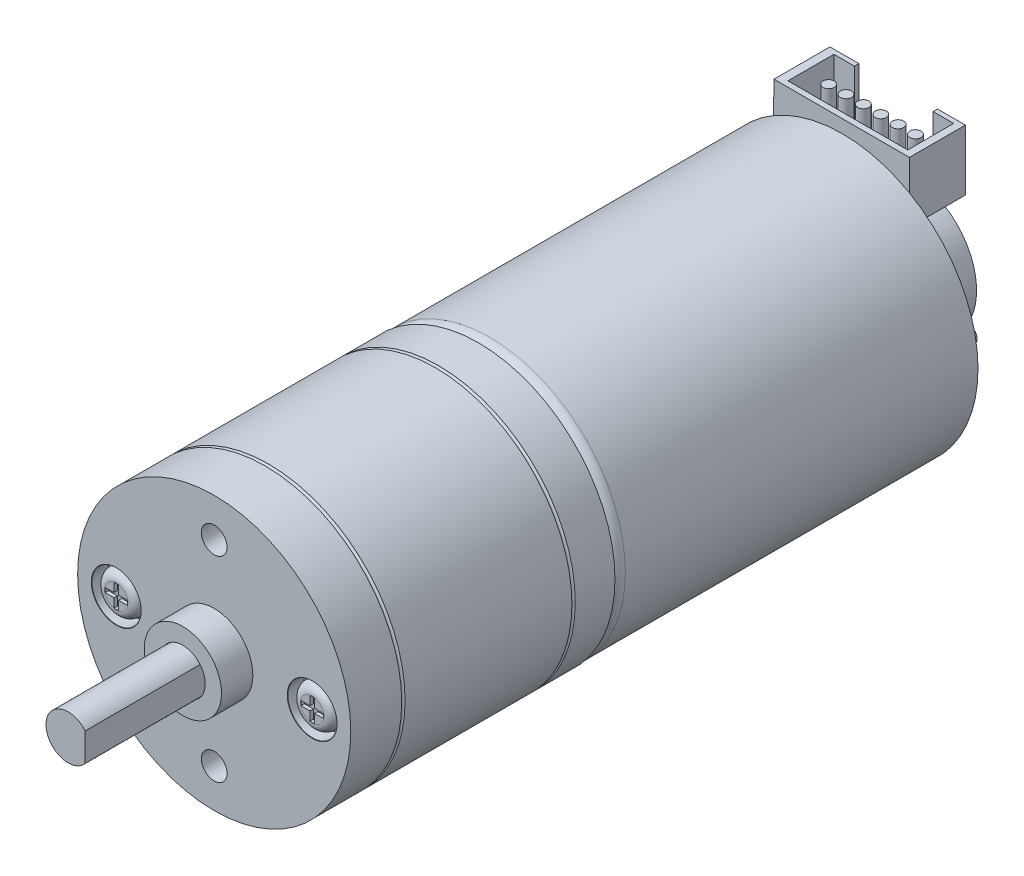
SolidWorks part; units mm, degrees
ref_plane "Front Plane" through (0, 0, 0) normal (0, 0, 1) x (1, 0, 0)
ref_plane "Top Plane" through (0, 0, 0) normal (0, 1, 0) x (1, 0, 0)
ref_plane "Right Plane" through (0, 0, 0) normal (1, 0, 0) x (0, 0, -1)
sketch "Sketch1" plane through (0, 0, 0) normal (0, 0, 1) x (1, 0, 0)
  circle A0 centre (0, 0) radius 12.125
  dimension "D1" = 24.25
extrude "Boss-Extrude1" add sketch "Sketch1" along normal blind 31
sketch "Sketch2" plane through (0, 0, 0) normal (0, 0, -1) x (-1, 0, 0)
  circle A1 centre (0, 0) radius 12.125
  circle A2 centre (0, 0) radius 12.125
  dimension "D1" = 0
fillet "Fillet2" radius 1 1 edges at (12.125, 0, 31)
shell "Shell1" thickness 1 removed face at (11.125, 0, 31)
ref_plane "Plane2" through (0, 0, 31) normal (0, 0, 1) x (1, 0, 0)
sketch "Sketch11" plane through (0, 0, 31) normal (0, 0, 1) x (1, 0, 0)
  circle A0 centre (0, 0) radius 12.2
  dimension "D1" = 24.4
extrude "Boss-Extrude4" add sketch "Sketch11" along normal blind 23.6 separate body
sketch "Sketch12" plane through (0, 0, 54.6) normal (0, 0, 1) x (1, 0, 0)
  circle A0 centre (0, 0) radius 3.45
  circle A1 centre (0, 0) radius 2
  dimension "D1" = 6.9
  dimension "D2" = 4
extrude "Boss-Extrude5" add sketch "Sketch12" along normal blind 2.8
sketch "Sketch14" plane through (0, 0, 54.6) normal (0, 0, 1) x (1, 0, 0)
  circle A0 centre (0, 0) radius 1.975
  dimension "D1" = 3.95
extrude "Boss-Extrude6" add sketch "Sketch14" along normal blind 13.05
sketch "Sketch16" plane through (0, 0, 67.65) normal (0, 0, 1) x (1, 0, 0)
  line L0 (-1.975, 0) -> (1.525, 0) construction
  line L1 (1.525, 0) -> (1.525, 1.255)
  line L2 (1.525, 0) -> (1.525, -1.255)
  circle A0 centre (0, 0) radius 1.975 construction
  arc A1 (1.525, -1.255) -> (1.525, 1.255) centre (0, 0) ccw
  dimension "D1" = 3.5
extrude "Cut-Extrude5" cut sketch "Sketch16" against normal up to surface (13.05 mm away) up to face at (3.45, 0, 54.6)
sketch "Sketch17" plane through (0, 0, 0) normal (0, 1, 0) x (1, 0, 0)
  line L0 (-12.2, -54.6) -> (-12.2, -49.9) construction
  line L1 (-12.2, -31) -> (-12.2, -54.6) construction
  line L2 (-12.2, -31) -> (-12.2, -34.7) construction
  circle A0 centre (-12.2, -49.9) radius 0.15
  circle A1 centre (-12.2, -34.7) radius 0.15
  dimension "D2" = 0.3
  dimension "D1" = 4.7
ref_axis "Axis1" through (0, 0, 54.6) along (0, 0, -1)
revolve "Cut-Revolve1" cut sketch "Sketch17" angle 360 about axis through (0, 0, 54.6) along (0, 0, -1)
sketch "Sketch18" plane through (0, 0, 54.6) normal (0, 0, 1) x (1, 0, 0)
  line L0 (0, 0) -> (8.75, 0) construction
  line L1 (0, 0) -> (0, 8.75) construction
  circle A1 centre (0, 8.75) radius 1.15
  circle A3 centre (0, -8.75) radius 1.15
  dimension "D3" = 2.3
extrude "Cut-Extrude7" cut sketch "Sketch18" against normal blind 10
sketch "Sketch19" plane through (0, 0, 0) normal (1, 0, 0) x (0, 0, -1)
  line L0 (-54.6, 9.9) -> (-53.4944, 10.0329)
  line L1 (-54.6, 9.9) -> (-54.6, 7.6) construction
  line L2 (-54.6, 12.2) -> (-54.6, -12.2) construction
  line L3 (-53.4944, 10.0329) -> (-53.399, 9.9)
  line L4 (-53.399, 9.9) -> (-54.6, 9.9)
sketch "Sketch20" plane through (0, 0, 54.6) normal (0, 0, 1) x (1, 0, 0)
  circle A0 centre (0, 8.75) radius 1.1448
curve "Helix/Spiral1" pitch 0.5 height 6 turns 12
sketch "Sketch21" plane through (0, 0, 54.6) normal (0, 0, 1) x (1, 0, 0)
  line L0 (0, 0) -> (0, -5.9622) construction
  circle A1 centre (8.75, 0) radius 2.25
  circle A2 centre (-8.75, 0) radius 2.25
  dimension "D1" = 4.5
hole_wizard "CBORE for M2 Cheese Head Screw1" positions "3DSketch1" profile "Sketch23" counterbore size "M2" standard "DIN"
sketch3d "3DSketch1"
  point P0 (-8.75, 0, 54.6)
  point P3 (8.75, 0, 54.6)
sketch "Sketch23" plane through (-8.75, 0, 54.6) normal (1, 0, 0) x (0, -1, 0)
  line L0 (0, 0) -> (0, 5.7811)
  line L1 (0, 5.7811) -> (1.3, 5)
  line L2 (1.3, 5) -> (1.3, 1.4)
  line L3 (1.3, 1.4) -> (2.2, 1.4)
  line L5 (2.2, 1.4) -> (2.2, 0.025)
  line L6 (2.2, 0.025) -> (2.225, 0)
  line L7 (2.225, 0) -> (0, 0)
  line L8 (-2.2, 0.025) -> (-2.225, 0) construction
  line L10 (0, 5.7811) -> (-1.3, 5) construction
  line L11 (0, -6.35) -> (0, 107.95) construction
  dimension "Hole Dia." = 2.6
  dimension "Hole Depth" = 5
  dimension "C'Bore Dia." = 4.4
  dimension "C'Bore Depth" = 1.4
  dimension "Near C'Sink Dia." = 4.45
  dimension "Near C'Sink Angle" = 90
  dimension "Drill Angle" = 118
sketch "Sketch24" plane through (0, 0, 53.2) normal (0, 0, 1) x (1, 0, 0)
  circle A0 centre (-8.75, 0) radius 1.8422
extrude "Boss-Extrude7" add sketch "Sketch24" along normal blind 1.4
sketch "Sketch25" plane through (0, 0, 54.6) normal (0, 0, 1) x (1, 0, 0)
  line L0 (-8.55, 0.2) -> (-7.75, 0.2)
  line L1 (-9.75, 0.2) -> (-8.95, 0.2)
  line L2 (-9.75, 0.2) -> (-9.75, -0.2)
  line L3 (-9.75, -0.2) -> (-8.95, -0.2)
  line L4 (-7.75, 0.2) -> (-7.75, -0.2)
  line L7 (-8.95, 1) -> (-8.55, 1)
  line L8 (-8.95, 1) -> (-8.95, 0.2)
  line L9 (-8.95, -1) -> (-8.55, -1)
  line L10 (-8.55, 1) -> (-8.55, 0.2)
  line L12 (-8.55, -0.2) -> (-7.75, -0.2)
  line L13 (-8.95, -0.2) -> (-8.95, -1)
  line L16 (-8.55, -0.2) -> (-8.55, -1)
  point P0 (-8.75, 0)
  point P5 (-8.75, 0)
extrude "Cut-Extrude9" cut sketch "Sketch25" against normal blind 0.3
fillet "Fillet3" radius 0.8 1 edges at (-6.9078, 0, 54.6)
mirror "Mirror2" about plane through (0, 0, 0) normal (1, 0, 0) of "Fillet3", "Cut-Extrude9", "Boss-Extrude7"
ref_plane "Plane3" through (0, 0, 0) normal (0, 0, -1) x (-1, 0, 0)
sketch "Sketch26" plane through (0, 0, 0) normal (0, 0, -1) x (-1, 0, 0)
  circle A0 centre (0, 0) radius 12.125
extrude "Boss-Extrude8" add sketch "Sketch26" along normal blind 1.5
ref_plane "Plane4" through (0, 0, -1.5) normal (0, 0, -1) x (-1, 0, 0)
sketch "Sketch27" plane through (0, 0, -1.5) normal (0, 0, -1) x (-1, 0, 0)
  circle A0 centre (0, 0) radius 6
  dimension "D1" = 12
extrude "Boss-Extrude9" add sketch "Sketch27" along normal blind 5 from offset 1 separate body contours A0
sketch "Sketch28" plane through (0, 0, -1.5) normal (0, 0, -1) x (-1, 0, 0)
  circle A0 centre (0, 0) radius 0.75
extrude "Boss-Extrude10" add sketch "Sketch28" along normal blind 8 contours A0
sketch "Sketch29" plane through (0, 0, -1.5) normal (0, 0, -1) x (-1, 0, 0)
  line L1 (6.0994, 13.2874) -> (-6, 13.2874)
  line L2 (6.0994, 13.2874) -> (6.1786, 7.872)
  line L3 (6.1786, 7.872) -> (-6, 7.872)
  line L4 (-6, 13.2874) -> (-6, 7.872)
  line L5 (6.0994, 13.2874) -> (-6, 7.872) construction
  line L6 (6.1786, 7.872) -> (-6, 13.2874) construction
  point P0 (0, 10.0459)
  point P5 (0, 0)
extrude "Boss-Extrude11" add sketch "Sketch29" along normal blind 5
ref_plane "Plane5" through (0, 13.2874, 0) normal (0, 1, 0) x (1, 0, 0)
sketch "Sketch31" plane through (0, 13.2874, 0) normal (0, 1, 0) x (1, 0, 0)
  line L1 (5.3489, 6.1016) -> (-5.3489, 6.1016)
  line L2 (5.3489, 6.1016) -> (5.3489, 1.9988)
  line L3 (5.3489, 1.9988) -> (-5.3489, 1.9988)
  line L4 (-5.3489, 6.1016) -> (-5.3489, 1.9988)
  line L5 (5.3489, 6.1016) -> (-5.3489, 1.9988) construction
  line L6 (5.3489, 1.9988) -> (-5.3489, 6.1016) construction
  line L7 (3.5118, 10.53) -> (-3.5118, 10.53)
  line L8 (3.5118, 10.53) -> (3.5118, 3.7483)
  line L9 (3.5118, 3.7483) -> (-3.5118, 3.7483)
  line L10 (-3.5118, 10.53) -> (-3.5118, 3.7483)
  line L11 (3.5118, 10.53) -> (-3.5118, 3.7483) construction
  line L12 (3.5118, 3.7483) -> (-3.5118, 10.53) construction
  point P0 (0, 4.0502)
  point P5 (0, 7.1391)
  line M3 (6, 6.5) -> (-6.0994, 6.5)
extrude "Cut-Extrude10" cut sketch "Sketch31" against normal blind 4.5 contours L10 L1 L4 L3 L2 L8 L9 | L1 L10 L9 L8 | L10 L1 L8 M3 region at (0, 13.2874, -3.5218) region at (0, 13.2874, -4.9249) region at (0, 13.2874, -6.3008)
sketch "Sketch32" plane through (0, 8.7874, 0) normal (0, 1, 0) x (1, 0, 0)
  circle A0 centre (3.9803, 4.0556) radius 0.5
  circle A1 centre (2.4303, 4.0556) radius 0.5
  circle A2 centre (0.8803, 4.0556) radius 0.5
  circle A3 centre (-0.6697, 4.0556) radius 0.5
  circle A4 centre (-2.2197, 4.0556) radius 0.5
  circle A5 centre (-3.7697, 4.0556) radius 0.5
  point P2 (0, 0)
  dimension "D1" = 6
extrude "Boss-Extrude12" add sketch "Sketch32" along normal blind 4 contours A0 | A1 | A2 | A3 | A4 | A5
sketch "Sketch33" plane through (0, 0, -1.5) normal (0, 0, -1) x (-1, 0, 0)
  line L0 (5.822, -4.3383) -> (7.2246, -1.6864) construction
  line L1 (5.159, -3.9877) -> (6.5616, -1.3357)
  line L2 (6.485, -4.6889) -> (7.8876, -2.037)
  line L3 (-5.736, -4.291) -> (-7.2951, -1.7279) construction
  line L4 (-6.3768, -4.6808) -> (-7.9358, -2.1177)
  line L5 (-5.0952, -3.9012) -> (-6.6543, -1.3382)
  line L6 (0, 0) -> (0, -6.9518) construction
  line L7 (-8.5109, 0.5462) -> (-10.6566, 0.5462)
  line L8 (-8.5109, 0.5462) -> (-8.5109, -0.5462)
  line L9 (-8.5109, -0.5462) -> (-10.6566, -0.5462)
  line L10 (-10.6566, 0.5462) -> (-10.6566, -0.5462)
  line L11 (-8.5109, 0.5462) -> (-10.6566, -0.5462) construction
  line L12 (-8.5109, -0.5462) -> (-10.6566, 0.5462) construction
  line L13 (10.6566, 0.5462) -> (10.6566, -0.5462)
  line L14 (8.5109, -0.5462) -> (10.6566, -0.5462)
  line L15 (8.5109, 0.5462) -> (8.5109, -0.5462)
  line L16 (8.5109, 0.5462) -> (10.6566, 0.5462)
  line L17 (2.5787, -9.2868) -> (1.7583, -9.2868)
  line L18 (-2.5787, -7.2673) -> (-1.7583, -7.2673)
  line L19 (-2.5787, -7.2673) -> (-2.5787, -9.2868)
  line L20 (-2.5787, -9.2868) -> (-1.7583, -9.2868)
  line L21 (-1.7583, -7.2673) -> (-1.7583, -9.2868)
  line L22 (-2.5787, -7.2673) -> (-1.7583, -9.2868) construction
  line L23 (-2.5787, -9.2868) -> (-1.7583, -7.2673) construction
  line L24 (2.5787, -7.2673) -> (2.5787, -9.2868)
  line L25 (1.7583, -7.2673) -> (1.7583, -9.2868)
  line L26 (2.5787, -7.2673) -> (1.7583, -7.2673)
  arc A0 (5.159, -3.9877) -> (6.485, -4.6889) centre (5.822, -4.3383) ccw
  arc A1 (7.8876, -2.037) -> (6.5616, -1.3357) centre (7.2246, -1.6864) ccw
  arc A2 (-6.3768, -4.6808) -> (-5.0952, -3.9012) centre (-5.736, -4.291) ccw
  arc A3 (-6.6543, -1.3382) -> (-7.9358, -2.1177) centre (-7.2951, -1.7279) ccw
  point P2 (6.5233, -3.0123)
  point P7 (-6.5155, -3.0095)
  point P19 (-9.5838, 0)
  point P26 (-2.1685, -8.2771)
extrude "Boss-Extrude13" add sketch "Sketch33" along normal blind 4 contours L2 A1 L1 A0 | A3 L4 A2 L5 region at (-6.5233, -3.0123, -1.5)
extrude "Boss-Extrude14" add sketch "Sketch33<4>" along normal blind 1
sketch "Sketch33<4>" plane through (0, 0, -1.5) normal (0, 0, -1) x (-1, 0, 0) same geometry as "Sketch33"
